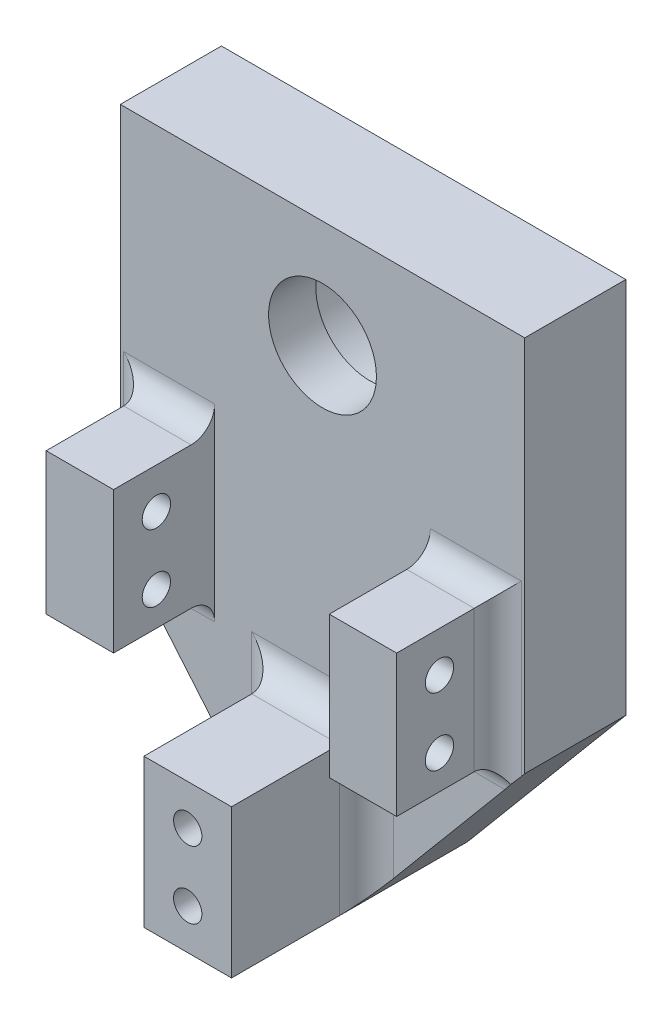
SolidWorks part; units mm, degrees
ref_plane "Front Plane" through (0, 0, 0) normal (0, 0, 1) x (1, 0, 0)
ref_plane "Top Plane" through (0, 0, 0) normal (0, 1, 0) x (1, 0, 0)
ref_plane "Right Plane" through (0, 0, 0) normal (1, 0, 0) x (0, 0, -1)
sketch "Sketch1" plane through (0, 0, 0) normal (0, 0, 1) x (1, 0, 0)
  line L1 (-30, -40) -> (30, -40)
  line L2 (-30, -40) -> (-30, 16)
  line L3 (-30, 16) -> (30, 16)
  line L4 (30, -40) -> (30, 16)
  circle A0 centre (0, 0) radius 8
  circle A3 centre (0, 0) radius 11 construction
  dimension "D1" = 16
  dimension "D2" = 22
  dimension "D3" = 60
  dimension "D4" = 16
  dimension "D5" = 30
  dimension "D6" = 40
extrude "Boss-Extrude1" add sketch "Sketch1" along normal blind 7
sketch "Sketch2" plane through (0, 0, 0) normal (0, 0, -1) x (-1, 0, 0)
  line L0 (-37.1992, 0) -> (52.0024, 0) construction
  line L1 (30, -40) -> (-30, -40) construction
  line L2 (30, 16) -> (30, -40) construction
  line L3 (-30, 16) -> (30, 16) construction
  line L4 (-30, -40) -> (-30, 16) construction
  line L5 (30, -40) -> (-30, -40)
  line L6 (30, 16) -> (30, -40)
  line L7 (-30, 16) -> (30, 16)
  line L8 (-30, -40) -> (-30, 16)
  circle A0 centre (0, 0) radius 11
  dimension "D1" = 22
extrude "Boss-Extrude2" add sketch "Sketch2" along normal blind 8
sketch "Sketch3" plane through (0, 0, 7) normal (0, 0, 1) x (1, 0, 0)
  line L0 (-16, -19) -> (-16, -40)
  line L1 (-16, -40) -> (-26, -40)
  line L2 (-26, -40) -> (-26, -19)
  line L3 (-26, -19) -> (-16, -19)
  line L4 (16, -19) -> (16, -40)
  line L5 (16, -40) -> (26, -40)
  line L6 (26, -40) -> (26, -19)
  line L7 (26, -19) -> (16, -19)
  line L8 (-21.8445, 35) -> (27.1513, 35) construction
  line L9 (-24.4362, -40) -> (27.9535, -40) construction
  dimension "D1" = 21
  dimension "D2" = 10
  dimension "D3" = 10
  dimension "D4" = 21
  dimension "D5" = 16
  dimension "D6" = 16
  dimension "D7" = 35
  dimension "D8" = 75
extrude "Boss-Extrude3" add sketch "Sketch3" along normal blind 15
sketch "Sketch4" plane through (-26, 0, 0) normal (-1, 0, 0) x (0, 0, 1)
  line L0 (15.65, -41.925) -> (15.65, -16.4347) construction
  line L1 (22, -19) -> (22, -40) construction
  line L2 (22, -40) -> (7, -40) construction
  circle A0 centre (15.65, -25) radius 2.1
  circle A1 centre (15.65, -35) radius 2.1
  dimension "D2" = 4.2
  dimension "D3" = 4.2
  dimension "D1" = 6.35
  dimension "D4" = 10
  dimension "D5" = 5
extrude "Cut-Extrude1" cut sketch "Sketch4" against normal through all
sketch "Sketch5" plane through (0, 0, 7) normal (0, 0, 1) x (1, 0, 0)
  line L0 (0, 0) -> (0, -62) construction
  line L1 (-16, -40) -> (16, -40) construction
  line L2 (-30, -40) -> (30, -40)
  line L3 (30, -40) -> (6.5, -68)
  line L4 (6.5, -68) -> (-6.5, -68)
  line L5 (-6.5, -68) -> (-30, -40)
  circle A0 centre (0, -52) radius 2.1
  circle A1 centre (0, -62) radius 2.1
  dimension "D3" = 10
  dimension "D1" = 4.2
  dimension "D2" = 4.2
  dimension "D4" = 12
  dimension "D5" = 6
  dimension "D6" = 13
  dimension "D7" = 6.5
extrude "Boss-Extrude4" add sketch "Sketch5" against normal through all
sketch "Sketch6" plane through (0, 0, -8) normal (0, 0, -1) x (-1, 0, 0)
  circle A0 centre (0, -52) radius 3.75
  circle A1 centre (0, -62) radius 3.75
  dimension "D1" = 7.5
  dimension "D2" = 7.5
extrude "Cut-Extrude2" [suppressed] cut sketch "Sketch6" against normal blind 5
fillet "Fillet2" radius 3.5 6 edges at (21, -19, 7) (26, -29.5, 7) (21, -40, 7) (-21, -19, 7) (-21, -40, 7) (-26, -29.5, 7)
sketch "Sketch7" plane through (0, 0, 7) normal (0, 0, 1) x (1, 0, 0)
  line L0 (-6.5, -68) -> (6.5, -68)
  line L1 (6.5, -68) -> (6.5, -46)
  line L2 (6.5, -46) -> (-6.5, -46)
  line L3 (-6.5, -46) -> (-6.5, -68)
  circle A0 centre (0, -62) radius 2.1 construction
  circle A1 centre (0, -52) radius 2.1 construction
  circle A2 centre (0, -62) radius 2.1
  circle A3 centre (0, -52) radius 2.1
  dimension "D1" = 6
extrude "Boss-Extrude5" add sketch "Sketch7" along normal blind 20
fillet "Fillet3" radius 4 3 edges at (6.5, -57, 7) (0, -46, 7) (-6.5, -57, 7)
equation "\"D6@Sketch3\"=\"D5@Sketch3\""
equation "\"D4@Sketch3\"=\"D1@Sketch3\""
equation "\"D2@Sketch5\"=\"D1@Sketch5\""
